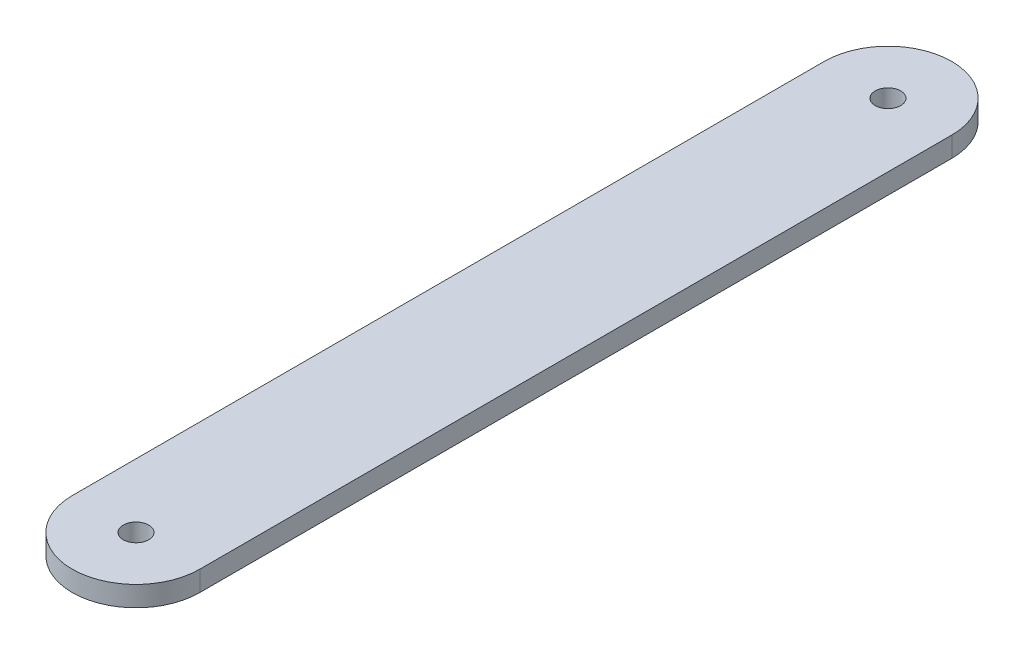
SolidWorks part; units mm, degrees
ref_plane "Front Plane" through (0, 0, 0) normal (0, 0, 1) x (1, 0, 0)
ref_plane "Top Plane" through (0, 0, 0) normal (0, 1, 0) x (1, 0, 0)
ref_plane "Right Plane" through (0, 0, 0) normal (1, 0, 0) x (0, 0, -1)
sketch "Sketch2" plane through (0, 0, 0) normal (0, 1, 0) x (1, 0, 0)
  line L0 (-5, 58.9716) -> (-5, 0)
  line L1 (5, 58.9716) -> (5, 0)
  circle A0 centre (0, 0) radius 1
  circle A1 centre (0, 58.9716) radius 1
  arc A2 (5, 0) -> (-5, 0) centre (0, 0) cw
  arc A3 (5, 58.9716) -> (-5, 58.9716) centre (0, 58.9716) ccw
  dimension "D2" = 2
  dimension "D3" = 5
  dimension "D1" = 58.9716
extrude "Boss-Extrude1" add sketch "Sketch2" along normal blind 1.5875
